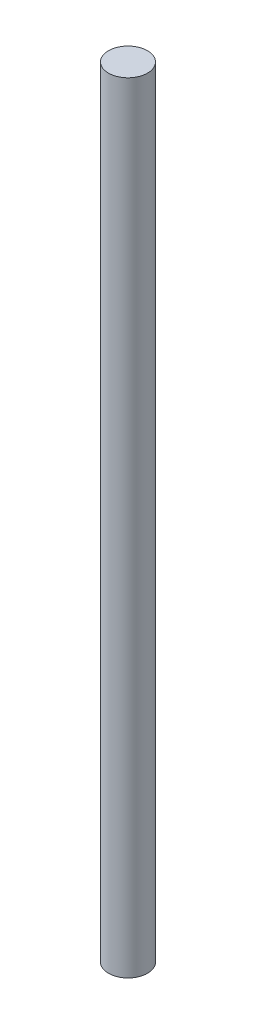
SolidWorks part; units mm, degrees
ref_plane "Front Plane" through (0, 0, 0) normal (0, 0, 1) x (1, 0, 0)
ref_plane "Top Plane" through (0, 0, 0) normal (0, 1, 0) x (1, 0, 0)
ref_plane "Right Plane" through (0, 0, 0) normal (1, 0, 0) x (0, 0, -1)
sketch "Sketch1" plane through (0, 0, 0) normal (0, 1, 0) x (1, 0, 0)
  circle A0 centre (0, 0) radius 2.5
  dimension "D1" = 5
extrude "Boss-Extrude1" add sketch "Sketch1" along normal blind 100.076
